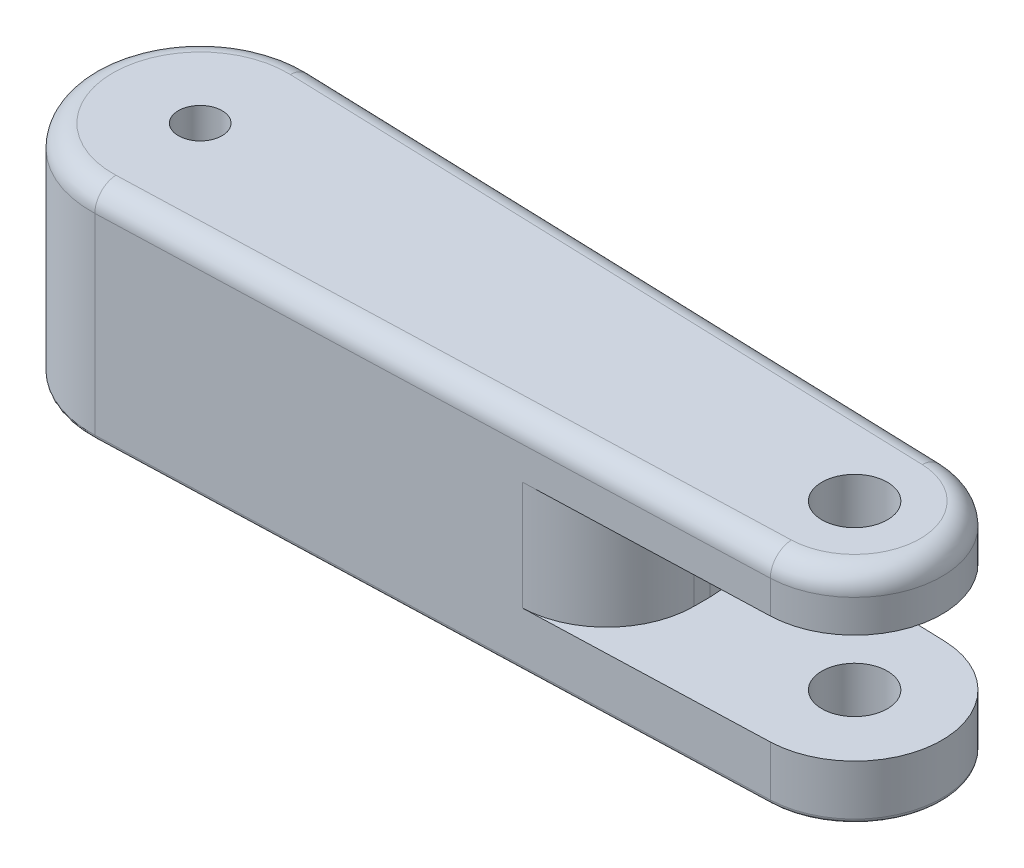
SolidWorks part; units mm, degrees
material "ABS"
ref_plane "Alzado" through (0, 0, 0) normal (0, 0, 1) x (1, 0, 0)
ref_plane "Planta" through (0, 0, 0) normal (0, 1, 0) x (1, 0, 0)
ref_plane "Vista lateral" through (0, 0, 0) normal (1, 0, 0) x (0, 0, -1)
sketch "Croquis1" plane through (0, 0, 0) normal (0, 1, 0) x (1, 0, 0)
  line L0 (0, 0) -> (-150, 0) construction
  line L1 (-149.1667, 24.9861) -> (0.6667, 19.9889)
  line L2 (0.6667, -19.9889) -> (-149.1667, -24.9861)
  arc A0 (0.6667, -19.9889) -> (0.6667, 19.9889) centre (0, 0) ccw
  arc A1 (-149.1667, 24.9861) -> (-149.1667, -24.9861) centre (-150, 0) ccw
  circle A2 centre (-150, 0) radius 5
  dimension "D1" = 40
  dimension "D2" = 50
  dimension "D4" = 10
  dimension "D3" = 150
extrude "Saliente-Extruir1" add sketch "Croquis1" along normal blind 25 and the other way blind 25
fillet "Redondeo9" radius 1 4 edges at (-175, -25, 0) (-74.25, -25, -22.4875) (20, -25, 0) (-74.25, -25, 22.4875)
sketch "Croquis3" plane through (0, 0, 0) normal (0, 0, 1) x (1, 0, 0)
  line L1 (-35, -12.5) -> (35, -12.5)
  line L2 (-35, -12.5) -> (-35, 12.5)
  line L3 (-35, 12.5) -> (35, 12.5)
  line L4 (35, -12.5) -> (35, 12.5)
  line L5 (-35, -12.5) -> (35, 12.5) construction
  line L6 (-35, 12.5) -> (35, -12.5) construction
  point P0 (0, 0)
  dimension "D1" = 25
  dimension "D2" = 70
extrude "Cortar-Extruir1" cut sketch "Croquis3" against normal blind 47 and the other way blind 49
fillet "Redondeo10" radius 20 2 edges at (-35, 0, -21.1784) (-35, 0, 21.1784)
sketch "Croquis4" plane through (0, 25, 0) normal (0, 1, 0) x (1, 0, 0)
  circle A0 centre (0, 0) radius 7.5
  dimension "D1" = 15
extrude "Cortar-Extruir2" cut sketch "Croquis4" against normal blind 65
fillet "Redondeo11" radius 5 4 edges at (20, 25, 0) (-74.25, 25, 22.4875) (-175, 25, 0) (-74.25, 25, -22.4875)
